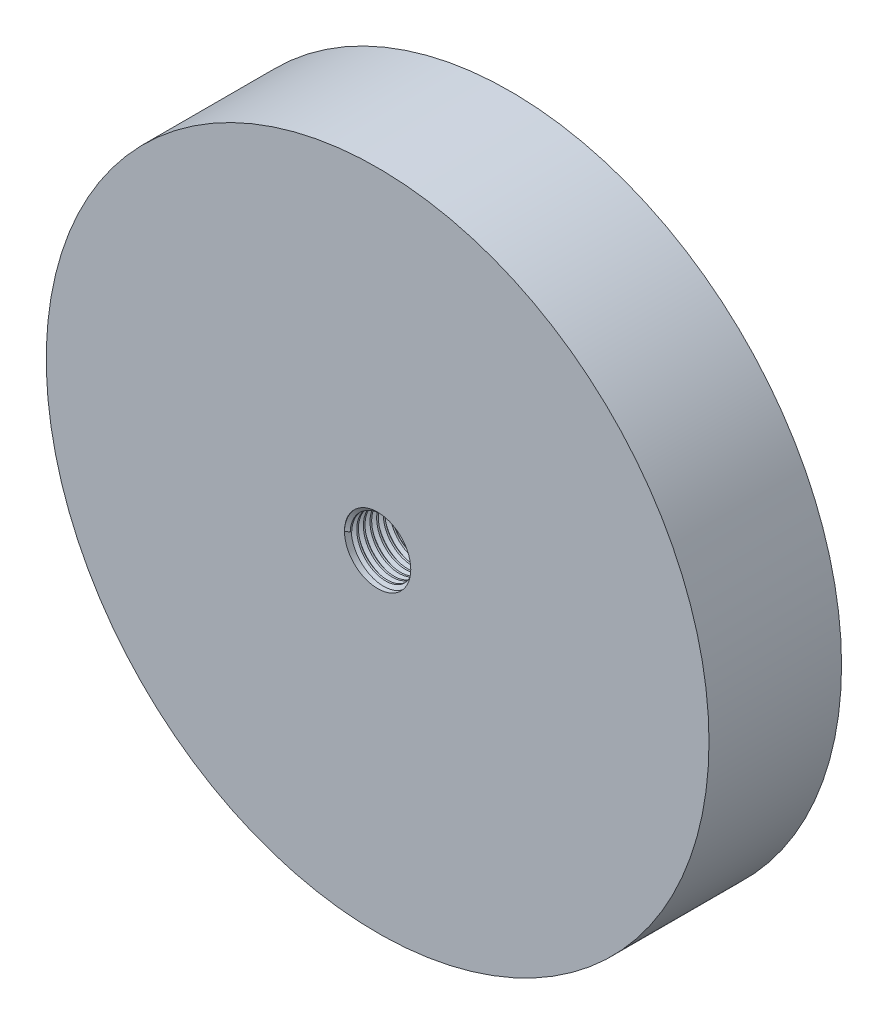
SolidWorks part; units mm, degrees
ref_plane "Front Plane" through (0, 0, 0) normal (0, 0, 1) x (1, 0, 0)
ref_plane "Top Plane" through (0, 0, 0) normal (0, 1, 0) x (1, 0, 0)
ref_plane "Right Plane" through (0, 0, 0) normal (1, 0, 0) x (0, 0, -1)
sketch "Sketch1" plane through (0, 0, 0) normal (0, 0, 1) x (1, 0, 0)
  circle A0 centre (0, 0) radius 50
  dimension "D1" = 100
extrude "Boss-Extrude1" add sketch "Sketch1" along normal blind 20
sketch "Sketch2" plane through (0, 0, 20) normal (0, 0, 1) x (1, 0, 0)
  circle A0 centre (0, 0) radius 5
  dimension "D1" = 10
extrude "Cut-Extrude2" cut sketch "Sketch2" against normal blind 10 contours A0
thread "Thread1" pitch 1 method extrude profile "Thread Profile3" start angle 0, offset 0, length 10, pitch 1, diameter 10
ref_plane "Plane3" through (-5, 0, 20) normal (0, -1, 0) x (-1, 0, 0)
sketch "Thread Profile3" plane through (-5, 0, 20) normal (0, -1, 0) x (-1, 0, 0)
  line L0 (0, 0) -> (0, 1) construction
  line L11 (0, 0) -> (0, 0.875)
  line L12 (0, 0.875) -> (-0.5413, 0.5625)
  line L13 (-0.5413, 0.5625) -> (-0.5413, 0.3125)
  line L15 (-0.5413, 0.3125) -> (0, 0)
  line L17 (-0.5413, 0.4375) -> (0, 0.4375) construction
  point P2 (0, 0)
  dimension "Pitch" = 1
  dimension "Profile_Angle" = 60
  dimension "Profile_Land" = 0.25
  dimension "Profile_Height" = 0.5413
sketch "Sketch15" plane through (0, 0, 10) normal (0, 0, 1) x (1, 0, 0)
  circle A0 centre (0, 0) radius 5
  dimension "D1" = 10
extrude "Cut-Extrude3" cut sketch "Sketch15" against normal blind 2
